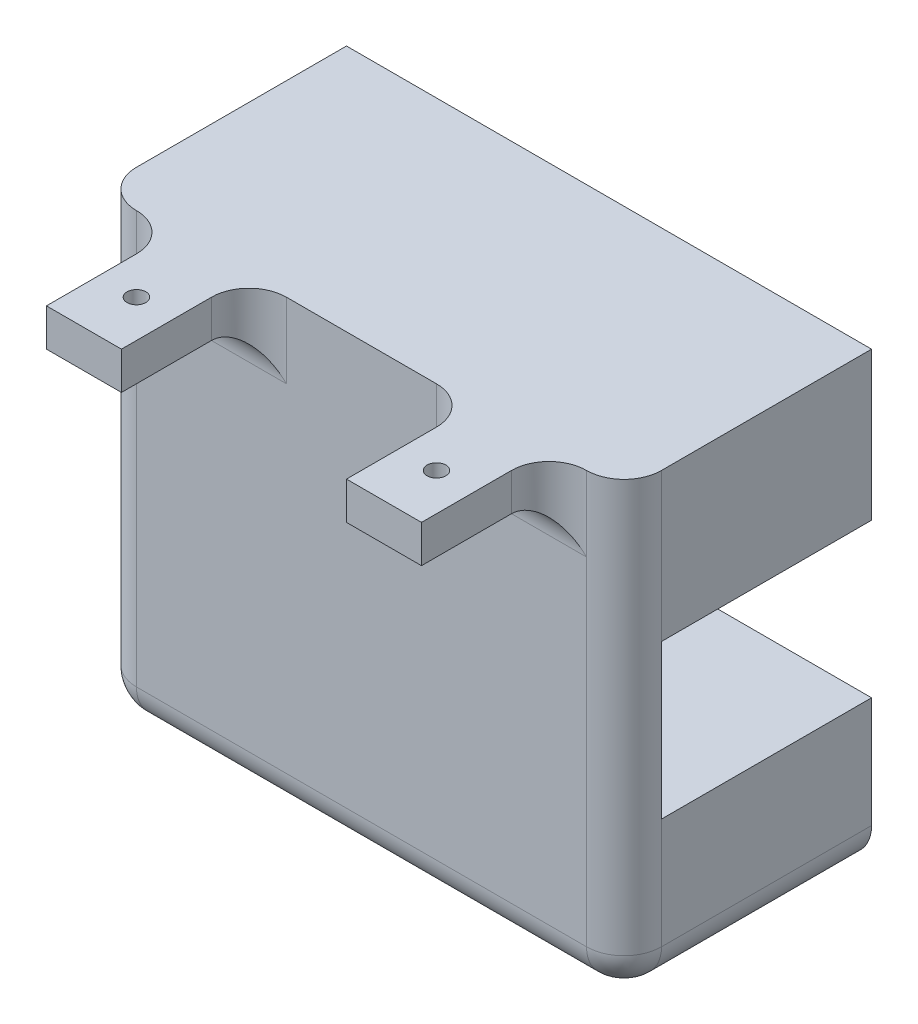
SolidWorks part; units mm, degrees
ref_plane "正面" through (0, 0, 0) normal (0, 0, 1) x (1, 0, 0)
ref_plane "平面" through (0, 0, 0) normal (0, 1, 0) x (1, 0, 0)
ref_plane "右側面" through (0, 0, 0) normal (1, 0, 0) x (0, 0, -1)
sketch "ｽｹｯﾁ2" plane through (0, 0, 0) normal (0, 0, 1) x (1, 0, 0)
  line L1 (-35, 30) -> (35, 30)
  line L2 (-35, 30) -> (-35, -30)
  line L3 (-35, -30) -> (35, -30)
  line L4 (35, 30) -> (35, -30)
  line L5 (-35, 30) -> (35, -30) construction
  line L6 (-35, -30) -> (35, 30) construction
  line L11 (-1.1602, 0.9945) -> (26.8884, -23.0472) construction
  line L12 (-15.8388, -9.5033) -> (15.8388, 9.5033) construction
  point P0 (0, 0)
  point P6 (0, 0)
  dimension "D1" = 70
  dimension "D2" = 60
extrude "ﾎﾞｽ - 押し出し2" add sketch "ｽｹｯﾁ2" along normal blind 33
sketch "ｽｹｯﾁ3" plane through (0, 0, 0) normal (0, 0, 1) x (1, 0, 0)
  line L1 (-20.35, 10.25) -> (20.35, 10.25)
  line L2 (-20.35, 10.25) -> (-20.35, -10.25)
  line L3 (-20.35, -10.25) -> (20.35, -10.25)
  line L4 (20.35, 10.25) -> (20.35, -10.25)
  line L5 (-20.35, 10.25) -> (20.35, -10.25) construction
  line L6 (-20.35, -10.25) -> (20.35, 10.25) construction
  point P0 (0, 0)
  dimension "D1" = 40.7
  dimension "D2" = 20.5
extrude "ｶｯﾄ - 押し出し1" cut sketch "ｽｹｯﾁ3" along normal blind 28 contours L2 L1 L4 L3
sketch "ｽｹｯﾁ4" plane through (0, 0, 0) normal (0, 0, 1) x (1, 0, 0)
  line L0 (20.35, 10.25) -> (35, 10.25)
  line L1 (35, -30) -> (35, 30) construction
  line L2 (35, 10.25) -> (35, -10.25)
  line L3 (35, -10.25) -> (20.35, -10.25)
  line L4 (20.35, -10.25) -> (20.35, 10.25)
extrude "ﾎﾞｽ - 押し出し3" add sketch "ｽｹｯﾁ4" along normal blind 28
sketch "ｽｹｯﾁ5" plane through (0, 0, 0) normal (0, 0, 1) x (1, 0, 0)
  line L0 (20.35, 10.25) -> (35, 10.25)
  line L1 (35, -30) -> (35, 30) construction
  line L2 (35, 10.25) -> (35, -10.25)
  line L3 (35, -10.25) -> (20.35, -10.25)
  line L4 (20.35, -10.25) -> (20.35, 10.25)
extrude "ｶｯﾄ - 押し出し4" cut sketch "ｽｹｯﾁ5" along normal blind 28
sketch "ｽｹｯﾁ6" plane through (0, 0, 0) normal (0, 0, 1) x (1, 0, 0)
  line L0 (-25, -30) -> (-25, -25)
  line L1 (-35, -30) -> (35, -30) construction
  line L2 (-25, -25) -> (-15, -25)
  line L3 (-15, -25) -> (-15, -30)
  line L4 (-15, -30) -> (-25, -30)
  line L5 (15, -25) -> (15, -30)
  line L6 (15, -30) -> (25, -30)
  line L7 (25, -30) -> (25, -25)
  line L8 (25, -25) -> (15, -25)
  dimension "D1" = 15
  dimension "D2" = 10
  dimension "D3" = 15
  dimension "D4" = 10
  dimension "D5" = 5
  dimension "D6" = 5
sketch "ｽｹｯﾁ8" plane through (0, 0, 0) normal (0, 0, 1) x (1, 0, 0)
  line L0 (-25, 30) -> (-25, 25)
  line L1 (35, 30) -> (-35, 30) construction
  line L2 (-25, 25) -> (-15, 25)
  line L3 (-15, 25) -> (-15, 30)
  line L4 (-15, 30) -> (-25, 30)
  line L5 (15, 30) -> (15, 25)
  line L6 (15, 25) -> (25, 25)
  line L7 (25, 25) -> (25, 30)
  line L8 (25, 30) -> (15, 30)
  dimension "D1" = 15
  dimension "D2" = 10
  dimension "D3" = 5
  dimension "D4" = 5
  dimension "D5" = 10
  dimension "D6" = 10
  dimension "D7" = 15
extrude "ﾎﾞｽ - 押し出し5" add sketch "ｽｹｯﾁ8" along normal blind 50
hole_wizard "M3x0.5 ねじ穴1" positions "ｽｹｯﾁ9" profile "ｽｹｯﾁ10" tap size "M3x0.5" standard "JIS" end condition through all
sketch "ｽｹｯﾁ9" plane through (0, 30, 0) normal (0, 1, 0) x (1, 0, 0)
  line L1 (15, -33) -> (-15, -33) construction
  line L2 (35, -33) -> (25, -33) construction
  point P0 (-20, -43)
  point P2 (20, -43)
  dimension "D1" = 10
  dimension "D2" = 10
  dimension "D3" = 20
  dimension "D4" = 20
sketch "ｽｹｯﾁ10" plane through (-20, 30, 43) normal (1, 0, 0) x (0, 0, 1)
  line L0 (0, 0) -> (0, 60)
  line L1 (0, 60) -> (1.25, 60)
  line L2 (1.25, 60) -> (1.25, 0)
  line L5 (1.25, 0) -> (0, 0)
  line L11 (0, -6.35) -> (0, 107.95) construction
  dimension "次ｻｰﾌｪｽまでのねじ下穴ﾄﾞﾘﾙ直径" = 2.5
  dimension "次ｻｰﾌｪｽまでのねじ下穴ﾄﾞﾘﾙの深さ" = 60
cosmetic thread "穴のねじ山1" parameters "D2"=3
cosmetic thread "穴のねじ山2" parameters "D2"=3
fillet "ﾌｨﾚｯﾄ1" radius 5 6 edges at (-25, 27.5, 33) (15, 27.5, 33) (-15, 27.5, 33) (25, 27.5, 33) (20, 25, 33) (-20, 25, 33)
fillet "ﾌｨﾚｯﾄ2" radius 5 4 edges at (35, 0, 33) (35, -30, 16.5) (0, -30, 33) (-35, 0, 33)
fillet "ﾌｨﾚｯﾄ3" radius 5 2 edges at (-33.5355, -28.5355, 31.5355) (-35, -30, 14)
